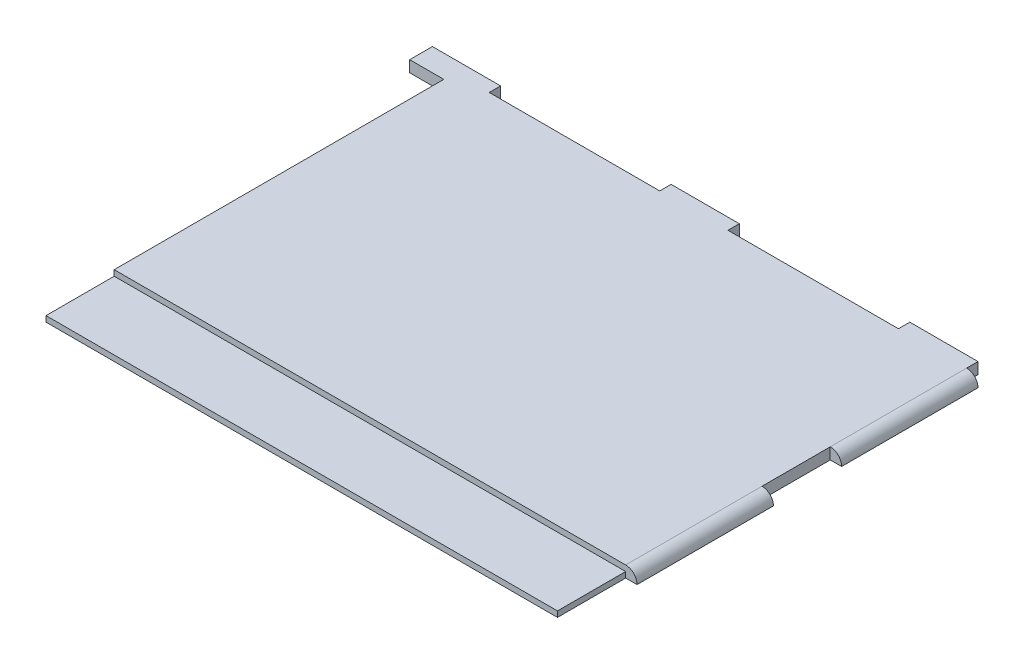
SolidWorks part; units mm, degrees
ref_plane "前基準面" through (0, 0, 0) normal (0, 0, 1) x (1, 0, 0)
ref_plane "上基準面" through (0, 0, 0) normal (0, 1, 0) x (1, 0, 0)
ref_plane "右基準面" through (0, 0, 0) normal (1, 0, 0) x (0, 0, -1)
sketch "草圖1" plane through (0, 0, 0) normal (0, 1, 0) x (1, 0, 0)
  line L0 (-36.2537, 43.5351) -> (203.7463, 43.5351)
  line L1 (203.7463, 43.5351) -> (203.7463, -286.4649)
  line L2 (198.7463, -286.4649) -> (198.7463, -256.4649)
  line L3 (198.7463, -256.4649) -> (183.2463, -256.4649)
  line L4 (183.2463, -256.4649) -> (183.2463, -266.4649)
  line L5 (183.2463, -266.4649) -> (124.7463, -266.4649)
  line L6 (124.7463, -266.4649) -> (124.7463, -262.4649)
  line L7 (124.7463, -262.4649) -> (109.2463, -262.4649)
  line L8 (109.2463, -262.4649) -> (109.2463, -266.4649)
  line L9 (109.2463, -266.4649) -> (-21.2537, -266.4649)
  line L10 (-21.2537, -266.4649) -> (-21.2537, 38.5351)
  line L11 (-21.2537, 38.5351) -> (-36.2537, 38.5351)
  line L12 (-36.2537, 38.5351) -> (-36.2537, 43.5351)
  line L13 (198.7463, -286.4649) -> (203.7463, -286.4649)
  line L15 (203.7463, -286.4649) -> (208.7463, -286.4649)
  line L16 (203.7463, -286.4649) -> (203.7463, -226.4649)
  line L17 (203.7463, -226.4649) -> (208.7463, -226.4649)
  line L18 (208.7463, -286.4649) -> (208.7463, -226.4649)
  line L19 (-36.2537, 43.5351) -> (-6.2537, 43.5351)
  line L20 (-36.2537, 43.5351) -> (-36.2537, 48.5351)
  line L21 (-36.2537, 48.5351) -> (-6.2537, 48.5351)
  line L22 (-6.2537, 43.5351) -> (-6.2537, 48.5351)
  line L23 (203.7463, 43.5351) -> (173.7463, 43.5351)
  line L24 (203.7463, 43.5351) -> (203.7463, 48.5351)
  line L25 (203.7463, 48.5351) -> (173.7463, 48.5351)
  line L26 (173.7463, 43.5351) -> (173.7463, 48.5351)
  line L27 (203.7463, 43.5351) -> (208.7463, 43.5351)
  line L28 (203.7463, 43.5351) -> (203.7463, -16.4649)
  line L29 (203.7463, -16.4649) -> (208.7463, -16.4649)
  line L30 (208.7463, 43.5351) -> (208.7463, -16.4649)
  line L31 (83.7463, 43.5351) -> (98.7463, 43.5351)
  line L32 (83.7463, 43.5351) -> (83.7463, 48.5351)
  line L33 (83.7463, 48.5351) -> (98.7463, 48.5351)
  line L34 (98.7463, 43.5351) -> (98.7463, 48.5351)
  line L35 (83.7463, 43.5351) -> (68.7463, 43.5351)
  line L36 (83.7463, 43.5351) -> (83.7463, 48.5351)
  line L37 (83.7463, 48.5351) -> (68.7463, 48.5351)
  line L38 (68.7463, 43.5351) -> (68.7463, 48.5351)
  line L39 (203.7463, -46.4649) -> (208.7463, -46.4649)
  line L40 (203.7463, -46.4649) -> (203.7463, -106.4649)
  line L41 (203.7463, -106.4649) -> (208.7463, -106.4649)
  line L42 (208.7463, -46.4649) -> (208.7463, -106.4649)
  line L43 (203.7463, -136.4649) -> (208.7463, -136.4649)
  line L44 (203.7463, -136.4649) -> (203.7463, -196.4649)
  line L45 (203.7463, -196.4649) -> (208.7463, -196.4649)
  line L46 (208.7463, -136.4649) -> (208.7463, -196.4649)
  dimension "D3" = 5
  dimension "D1" = 240
  dimension "D2" = 330
  dimension "D4" = 15
  dimension "D5" = 130.5
  dimension "D6" = 4
  dimension "D7" = 4
  dimension "D8" = 15.5
  dimension "D9" = 58.5
  dimension "D10" = 10
  dimension "D11" = 15.5
  dimension "D12" = 30
  dimension "D13" = 5
  dimension "D14" = 60
  dimension "D15" = 5
  dimension "D16" = 5
  dimension "D17" = 30
  dimension "D18" = 5
  dimension "D19" = 30
  dimension "D20" = 60
  dimension "D21" = 5
  dimension "D22" = 5
  dimension "D23" = 15
  dimension "D24" = 5
  dimension "D25" = 15
  dimension "D26" = 60
  dimension "D27" = 5
  dimension "D28" = 30
  dimension "D29" = 60
  dimension "D30" = 5
  dimension "D31" = 30
  dimension "D32" = 30
extrude "填料-伸長1" add sketch "草圖1" along normal blind 5 contours L2 L13 L1 L0 L12 L11 L10 L9 L8 L7 L6 L5 L4 L3 | L15 L18 L17 L1 | L30 L27 L1 L29 | L26 L0 L24 L25 | L0 L22 L21 L20 | L32 L33 L34 L31 | L36 L37 L38 L35 | L46 L45 L44 L43 | L42 L41 L40 L39 region at (-21.2537, 0, -46.0351) region at (91.0303, 0, 111.0679) region at (188.7463, 0, -46.0351) region at (206.2463, 0, -13.5351) region at (206.2463, 0, 256.4649)
fillet "圓角1" radius 5 4 edges at (208.7463, 5, -13.5351) (208.7463, 5, 76.4649) (208.7463, 5, 166.4649) (208.7463, 5, 256.4649)
sketch "草圖2" plane through (0, 5, 0) normal (0, 1, 0) x (1, 0, 0)
  line L1 (208.7463, -136.4649) -> (-30.7437, -136.4649)
  line L2 (208.7463, -136.4649) -> (208.7463, -291.2165)
  line L3 (208.7463, -291.2165) -> (-30.7437, -291.2165)
  line L4 (-30.7437, -136.4649) -> (-30.7437, -291.2165)
extrude "除料-伸長1" cut sketch "草圖2" against normal through all
sketch "草圖3" plane through (203.7463, 0, 0) normal (1, 0, 0) x (0, 0, -1)
  line L1 (-136.4649, 5) -> (-106.4649, 5)
  line L2 (-136.4649, 5) -> (-136.4649, 2.5)
  line L3 (-136.4649, 2.5) -> (-106.4649, 2.5)
  line L4 (-106.4649, 5) -> (-106.4649, 2.5)
  line L5 (-106.4649, 0) -> (-106.4649, 5) construction
  dimension "D1" = 2.5
  dimension "D2" = 30
extrude "除料-伸長2" cut sketch "草圖3" against normal through all
